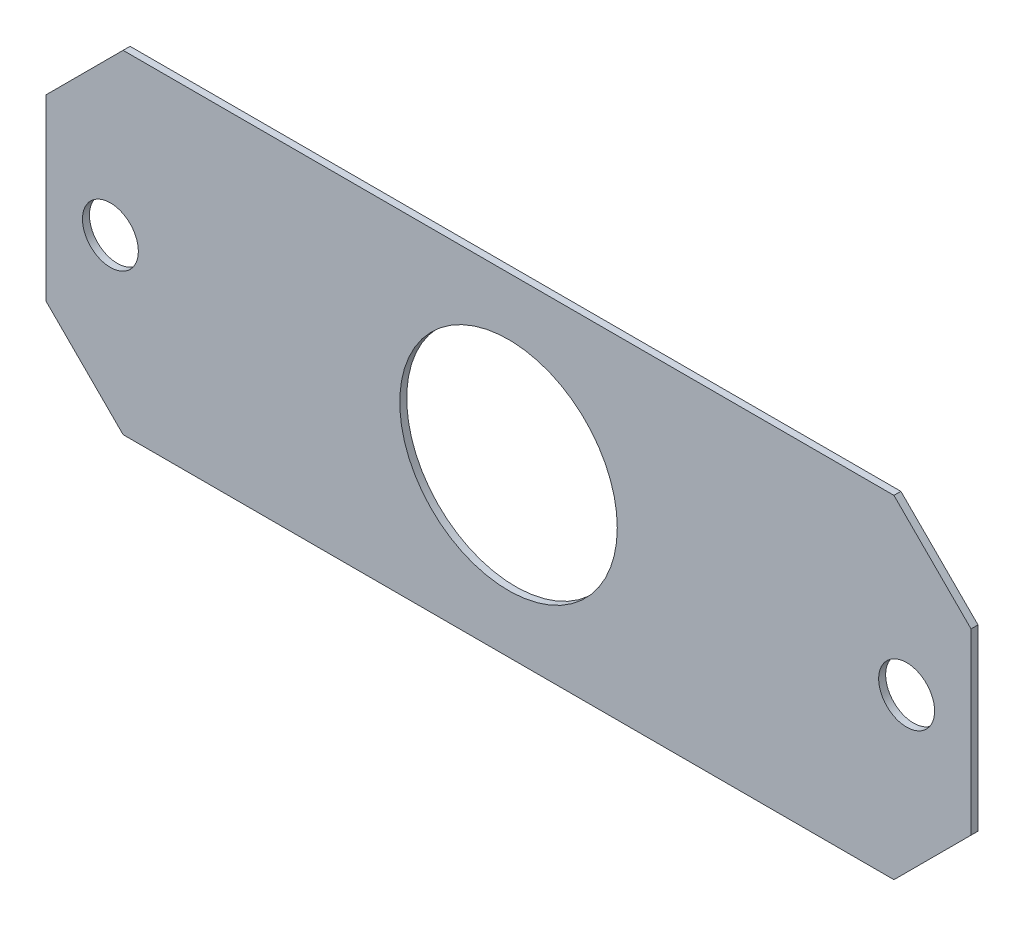
SolidWorks part; units mm, degrees
ref_plane "Front Plane" through (0, 0, 0) normal (0, 0, 1) x (1, 0, 0)
ref_plane "Top Plane" through (0, 0, 0) normal (0, 1, 0) x (1, 0, 0)
ref_plane "Right Plane" through (0, 0, 0) normal (1, 0, 0) x (0, 0, -1)
sketch "Sketch1" plane through (0, 0, 0) normal (0, 0, 1) x (1, 0, 0)
  line L0 (0, -55) -> (0, 55) construction
  line L1 (22.4995, 9.7155) -> (27.0002, 5.2148)
  line L2 (27.0002, 5.2148) -> (27.0002, -5.2148)
  line L3 (27.0002, -5.2148) -> (22.4995, -9.7155)
  line L4 (22.4995, -9.7155) -> (-22.4995, -9.7155)
  line L5 (-22.4995, -9.7155) -> (-27.0002, -5.2148)
  line L6 (-27.0002, -5.2148) -> (-27.0002, 5.2148)
  line L7 (-27.0002, 5.2148) -> (-22.4995, 9.7155)
  line L8 (-22.4995, 9.7155) -> (22.4995, 9.7155)
  line L9 (55, 0) -> (-55, 0) construction
  point P0 (-27.0002, 0)
  point P1 (27.0002, 0)
  point P8 (0, -9.7155)
  point P11 (0, 9.7155)
  dimension "D1" = 54.0004
  dimension "D2" = 19.431
extrude "Boss-Extrude1" add sketch "Sketch1" along normal blind 0.4064
sketch "Sketch2" plane through (0, 0, 0.4064) normal (0, 0, 1) x (1, 0, 0)
  line L0 (0.2235, 0) -> (-0.2235, 0) construction
  line L1 (-23.241, 0) -> (23.241, 0) construction
  line L2 (0, -0.2235) -> (0, 0.2235) construction
  point P0 (-23.241, 0)
  point P1 (23.241, 0)
  point P7 (0, 0)
  dimension "D1" = 46.482
hole_wizard "#4 Clearance Hole1" positions "Sketch3" profile "Sketch4" hole size "#4" standard "ANSI Inch" end condition through all
sketch "Sketch3" plane through (0, 0, 0.4064) normal (0, 0, 1) x (1, 0, 0)
  point P0 (-23.241, 0)
  point P3 (23.241, 0)
sketch "Sketch4" plane through (-23.241, 0, 0.4064) normal (1, 0, 0) x (0, -1, 0)
  line L0 (0, 0) -> (0, 0.4064)
  line L1 (0, 0.4064) -> (1.632, 0.4064)
  line L2 (1.632, 0.4064) -> (1.6319, 0)
  line L5 (1.6319, 0) -> (0, 0)
  line L11 (0, -6.35) -> (0, 107.95) construction
  dimension "Thru Hole Dia." = 3.2639
  dimension "Thru Hole Depth" = 0.4064
sketch "Sketch5" plane through (0, 0, 0.4064) normal (0, 0, 1) x (1, 0, 0)
  line L1 (-23.241, 0) -> (23.241, 0) construction
  circle A0 centre (0, 0) radius 6.35
  point P0 (0, 0)
  dimension "D1" = 12.7
extrude "Cut-Extrude1" cut sketch "Sketch5" against normal blind 0.4064
equation "\"distance holes\"= 1.830000in"
equation "\"D1@Sketch2\"=\"distance holes\""
